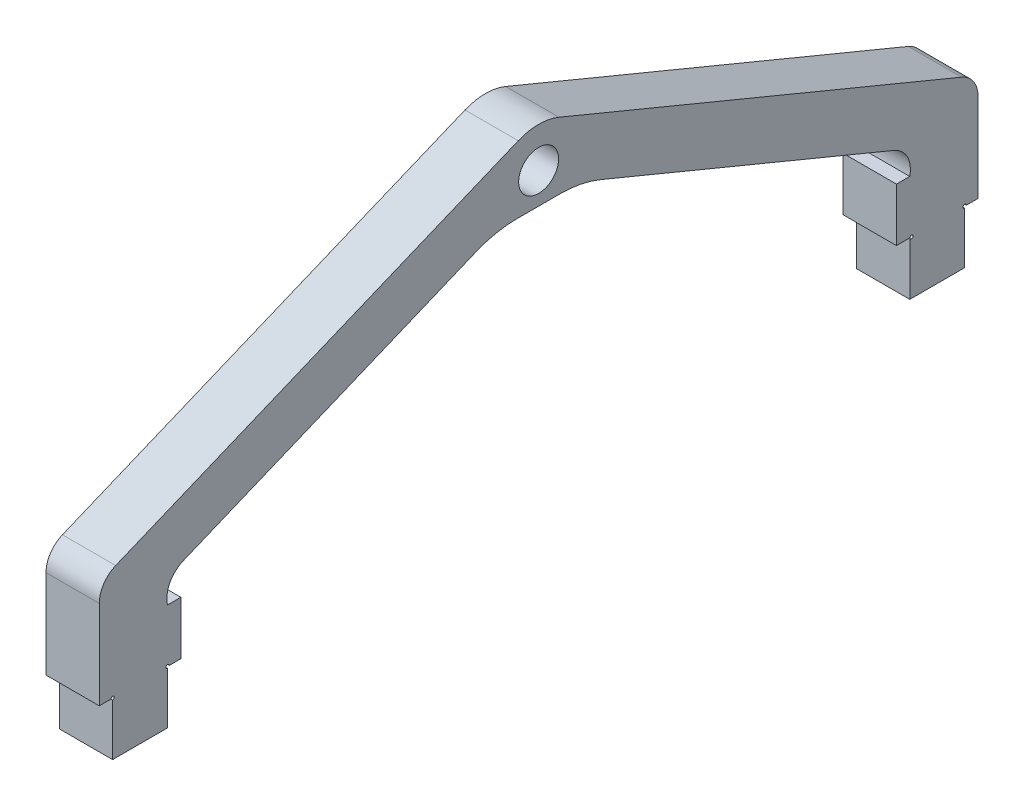
SolidWorks part; units mm, degrees
ref_plane "Front Plane" through (0, 0, 0) normal (0, 0, 1) x (1, 0, 0)
ref_plane "Top Plane" through (0, 0, 0) normal (0, 1, 0) x (1, 0, 0)
ref_plane "Right Plane" through (0, 0, 0) normal (1, 0, 0) x (0, 0, -1)
sketch "Sketch1" plane through (0, 0, 0) normal (1, 0, 0) x (0, 0, -1)
  line L0 (0, 0) -> (0, 25.4) construction
  line L1 (44.25, 0) -> (42.6625, 0) construction
  line L2 (50.8, 0) -> (52.3875, 0)
  line L3 (52.3875, 0) -> (52.3875, 12.7)
  line L4 (-50.8, 0) -> (-50.8, -6.35)
  line L5 (-50.8, -6.35) -> (-44.25, -6.35)
  line L6 (-44.25, 0) -> (-44.25, -6.35)
  line L7 (50.8, 0) -> (50.8, -6.35)
  line L8 (50.8, -6.35) -> (44.25, -6.35)
  line L9 (44.25, 0) -> (44.25, -6.35)
  line L10 (-44.25, 0) -> (-42.6625, 0)
  line L11 (5.0881, 25.4) -> (-5.0881, 25.4)
  line L13 (6.35, 31.75) -> (52.3875, 12.7)
  line L14 (-44.25, 6.35) -> (-42.6625, 6.35)
  line L15 (5.0881, 25.4) -> (46.0375, 8.4554)
  line L16 (44.25, 6.35) -> (46.0375, 8.4554)
  line L17 (3.9221, 25.8825) -> (46.0375, 8.4554) construction
  line L19 (46.0375, 0) -> (46.0375, 8.4554) construction
  line L20 (-6.35, 31.75) -> (-52.3875, 12.7)
  line L21 (-52.3875, 0) -> (-52.3875, 12.7)
  line L22 (-44.25, 6.35) -> (-46.0375, 8.4554)
  line L23 (-5.0881, 25.4) -> (-46.0375, 8.4554)
  line L24 (-50.8, 0) -> (-52.3875, 0)
  line L25 (-42.6625, 0) -> (-42.6625, 6.35)
  line L26 (42.6625, 0) -> (42.6625, 6.35)
  line L27 (42.6625, 6.35) -> (44.25, 6.35)
  line L28 (42.6625, 0) -> (44.25, 0)
  line L29 (-44.25, 6.35) -> (44.25, 6.35) construction
  line L30 (0, 0) -> (-44.25, 0) construction
  line L31 (-44.25, 0) -> (44.25, 0) construction
  line L32 (-6.35, 31.75) -> (0, 34.3776)
  line L33 (6.35, 31.75) -> (0, 34.3776)
  point P6 (0, 0)
  point P15 (-6.35, 25.4)
  point P16 (6.35, 25.4)
  point P17 (0, 25.4)
  dimension "D1" = 25.4
  dimension "D2" = 101.6
  dimension "D3" = 6.35
  dimension "D4" = 6.55
  dimension "D5" = 1.5875
  dimension "D6" = 6.35
  dimension "D8" = 12.7
  dimension "D10" = 1.5875
  dimension "D9" = 6.35
extrude "Boss-Extrude1" add sketch "Sketch1" along normal blind 6.35 contours L24 L4 L5 L6 L10 L9 L8 L7 L2 L3 L13 L20 L21 L23 L11 L15 L16 L14 L22 region at (0, -3.175, -49.6759)
sketch "Sketch2" plane through (6.35, 0, 0) normal (1, 0, 0) x (0, 0, -1)
  circle A0 centre (-50.8, 0) radius 0.1984
  circle A1 centre (-44.25, 0) radius 0.1984
  circle A2 centre (44.45, 0) radius 0.1984
  circle A3 centre (50.8, 0) radius 0.1984
  dimension "D1" = 0.3969
  dimension "D2" = 0.3969
extrude "Cut-Extrude1" cut sketch "Sketch2" against normal through all
fillet "Fillet5" radius 3.175 4 edges at (3.175, 8.4554, 46.0375) (3.175, 8.4554, -46.0375) (3.175, 12.7, -52.3875) (3.175, 12.7, 52.3875)
fillet "Fillet6" radius 12.7 2 edges at (3.175, 25.4, 5.0881) (3.175, 25.4, -5.0881)
fillet "Fillet7" radius 6.35 1 edges at (3.175, 34.3776, 0)
sketch "Sketch5" plane through (6.35, 0, 0) normal (1, 0, 0) x (0, 0, -1)
  circle A0 centre (0, 29.0929) radius 2.3813
  arc A1 (2.4279, 33.3729) -> (-2.4279, 33.3729) centre (0, 27.5054) ccw construction
  point P2 (0, 33.8554)
  dimension "D1" = 4.7625
extrude "Cut-Extrude6" cut sketch "Sketch5" against normal through all
